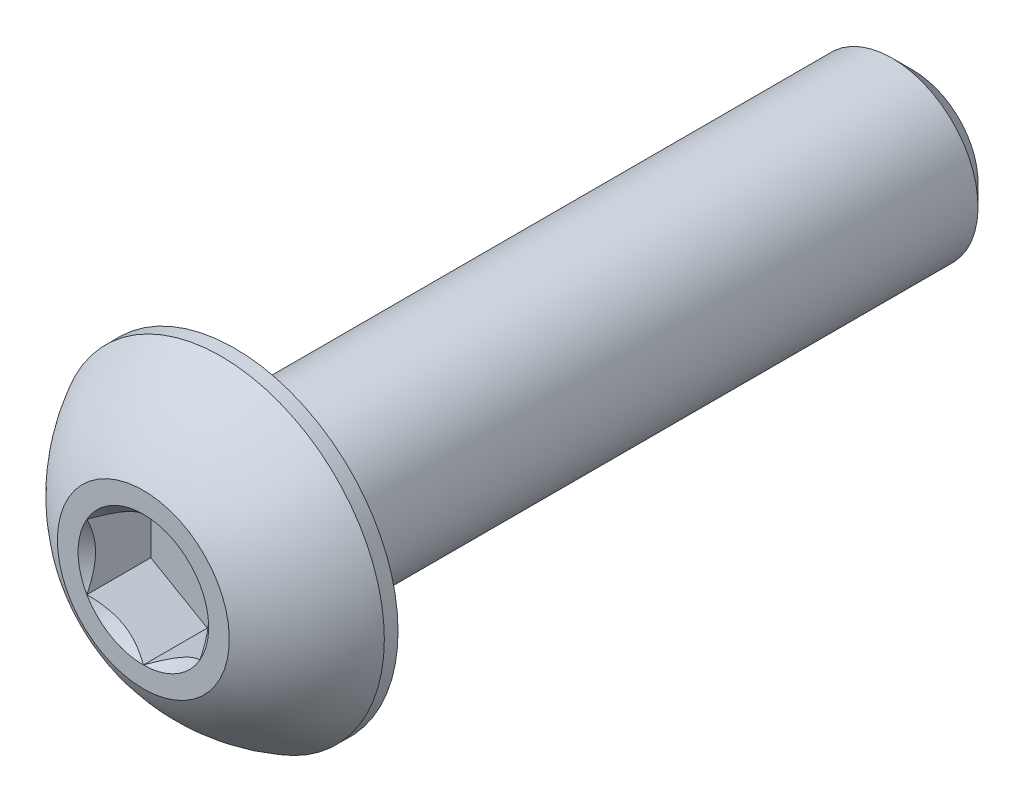
SolidWorks part; units mm, degrees
ref_plane "Front" through (0, 0, 0) normal (0, 0, 1) x (1, 0, 0)
ref_plane "Top" through (0, 0, 0) normal (0, 1, 0) x (1, 0, 0)
ref_plane "Right" through (0, 0, 0) normal (1, 0, 0) x (0, 0, -1)
sketch "Sketch1" plane through (0, 0, 0) normal (1, 0, 0) x (0, 0, -1)
  line L2 (2.5654, 2.413) -> (21.6154, 2.413)
  line L3 (21.6154, 2.413) -> (21.6154, 0)
  line L4 (21.6154, 0) -> (2.5654, 0)
  line L6 (2.1806, 4.5847) -> (2.5654, 4.5847) construction
  line L7 (21.6154, 2.413) -> (21.6154, -2.413) construction
  line L8 (0, 0) -> (2.5654, 0) construction
  line L9 (2.5654, 4.5847) -> (2.5654, -4.5847) construction
  line L11 (2.5654, 2.413) -> (2.5654, 0)
  line L13 (0, 1.5875) -> (0, -1.5875) construction
  line L14 (0, 1.5875) -> (0, 2.413) construction
  arc A3 (0, 2.413) -> (2.1806, 4.5847) centre (4.5749, 0) cw construction
  dimension "D1" = 0.3848
revolve "Revolve1" add sketch "Sketch1" angle 360 mid plane about L4
sketch "Sketch3" plane through (0, 0, -21.6154) normal (0, 0, -1) x (-1, 0, 0)
  circle A0 centre (0, 0) radius 2.413
curve "Helix/Spiral1" [suppressed] pitch 0.7937 height 19.8438 turns 25
sketch "Sketch2" plane through (0, 0, 0) normal (1, 0, 0) x (0, 0, -1)
  line L0 (21.6154, 2.413) -> (22.3099, 2.413)
  line L1 (22.3099, 2.413) -> (22.0123, 1.8974)
  line L2 (22.0123, 1.8974) -> (21.9131, 1.8974)
  line L3 (21.9131, 1.8974) -> (21.6154, 2.413)
  line L4 (21.7642, 2.1552) -> (22.1611, 2.1552) construction
  dimension "D1" = 60
  dimension "D2" = 0.0992
  dimension "D3" = 0.3969
chamfer "Chamfer1" distance 0.5953 angle 45 1 edges at (0, 2.413, -21.6154)
sweep "Cut-Sweep1" [suppressed] cut profiles "Sketch2" path "Helix/Spiral1"
sketch "Sketch7" plane through (0, 0, 0) normal (1, 0, 0) x (0, 0, -1)
  line L6 (2.1806, 4.5847) -> (2.5654, 4.5847) construction
  line L8 (0, 0) -> (2.5654, 0) construction
  line L11 (2.5654, 4.5847) -> (2.5654, -4.5847) construction
  line L12 (2.1806, 4.5847) -> (2.5654, 4.5847)
  line L13 (0, 0) -> (2.5654, 0)
  line L14 (0, 1.5875) -> (0, -1.5875) construction
  line L15 (2.5654, 4.5847) -> (2.5654, 0)
  line L16 (0, 2.413) -> (0, 0)
  arc A2 (2.1806, 4.5847) -> (0, 2.413) centre (4.5749, 0) ccw construction
  arc A3 (2.1806, 4.5847) -> (0, 2.413) centre (4.5749, 0) ccw
revolve "Revolve2" add sketch "Sketch7" angle 360 mid plane about L13
sketch "Sketch5" plane through (0, 0, 0) normal (0, 0, 1) x (1, 0, 0)
  line L1 (1.5875, -0.9165) -> (1.5875, 0.9165)
  line L2 (1.5875, 0.9165) -> (0, 1.8331)
  line L3 (0, 1.8331) -> (-1.5875, 0.9165)
  line L4 (-1.5875, 0.9165) -> (-1.5875, -0.9165)
  line L5 (-1.5875, -0.9165) -> (0, -1.8331)
  line L6 (0, -1.8331) -> (1.5875, -0.9165)
  circle A0 centre (0, 0) radius 1.5875 construction
extrude "Cut-Extrude2" cut sketch "Sketch5" against normal blind 1.7958
sketch "Sketch6" plane through (0, 0, 0) normal (0, 0, 1) x (1, 0, 0)
  circle A0 centre (0, 0) radius 1.8331
extrude "Cut-Extrude3" cut sketch "Sketch6" against normal blind 1.7958 draft 45
sketch "Sketch9" [suppressed] plane through (0, 0, -2.5654) normal (0, 0, 1) x (1, 0, 0)
  circle A2 centre (0, 0) radius 2.413
extrude "Boss-Extrude2" [suppressed] add sketch "Sketch9" against normal offset from surface (9.525 mm away) 31.75
sketch "Sketch10" plane through (0, 0, 0) normal (1, 0, 0) x (0, 0, -1)
  line L0 (21.6154, 2.413) -> (21.6154, -2.413) construction
  point P0 (20.4248, -2.413)
  dimension "D1" = 1.1906
equation "\"D3@Helix/Spiral1\" = \"Lg@Sketch1\" + \"D4@Helix/Spiral1\""
equation "\"D2@Sketch2\" = \"D4@Helix/Spiral1\" * .125"
equation "\"D3@Sketch2\" = \"D4@Helix/Spiral1\" * .5"
equation "\"D1@Chamfer1\" = \"D4@Helix/Spiral1\" * .75"
equation "\"D1@Cut-Extrude2\" = \"Head Ht@Sketch1\" * .7"
equation "\"D1@Sketch1\" = \"Head Ht@Sketch1\" * .15"
equation "\"D1@Sketch10\" = \"D4@Helix/Spiral1\" * 1.5"
equation "\"D1@Cut-Extrude3\" = \"D1@Cut-Extrude2\""
